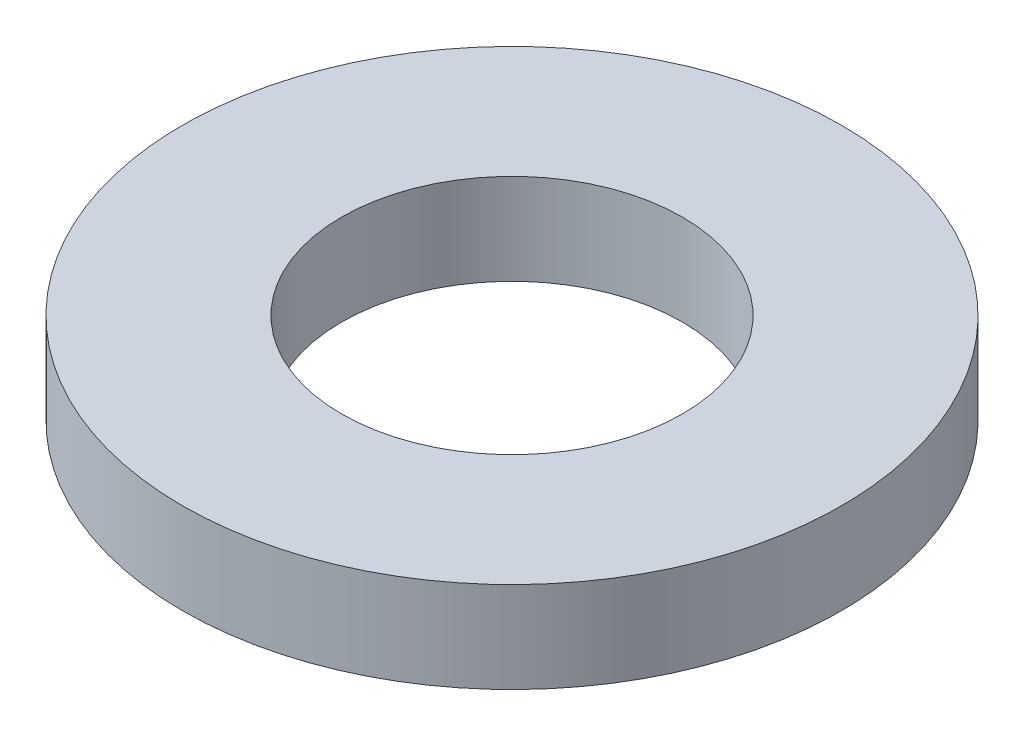
SolidWorks part; units mm, degrees
ref_plane "Front Plane" through (0, 0, 0) normal (0, 0, 1) x (1, 0, 0)
ref_plane "Top Plane" through (0, 0, 0) normal (0, 1, 0) x (1, 0, 0)
ref_plane "Right Plane" through (0, 0, 0) normal (1, 0, 0) x (0, 0, -1)
sketch "Sketch1" plane through (0, 0, 0) normal (0, 1, 0) x (1, 0, 0)
  circle A0 centre (0, 0) radius 72.5
  dimension "FLANGE_OD" = 145
extrude "Boss-Extrude1" add sketch "Sketch1" along normal blind 20
sketch "Sketch2" plane through (0, 0, 0) normal (0, 1, 0) x (1, 0, 0)
  circle A0 centre (0, 0) radius 37.5
  dimension "BORE_D" = 75
extrude "Cut-Extrude1" cut sketch "Sketch2" along normal through all
sketch "Sketch3" plane through (0, 20, 0) normal (0, 1, 0) x (1, 0, 0)
  circle A0 centre (0, 0) radius 30.5503 construction
  circle A1 centre (-30.5503, 0) radius 3.0554
  dimension "BOLT_D" = 6.1108
  dimension "BOLT_PCD" = 61.1006
extrude "Cut-Extrude2" cut sketch "Sketch3" against normal blind 14.166 rebuild error yes
pattern_circular "CirPattern1" count 8 over 360 rebuild error yes
